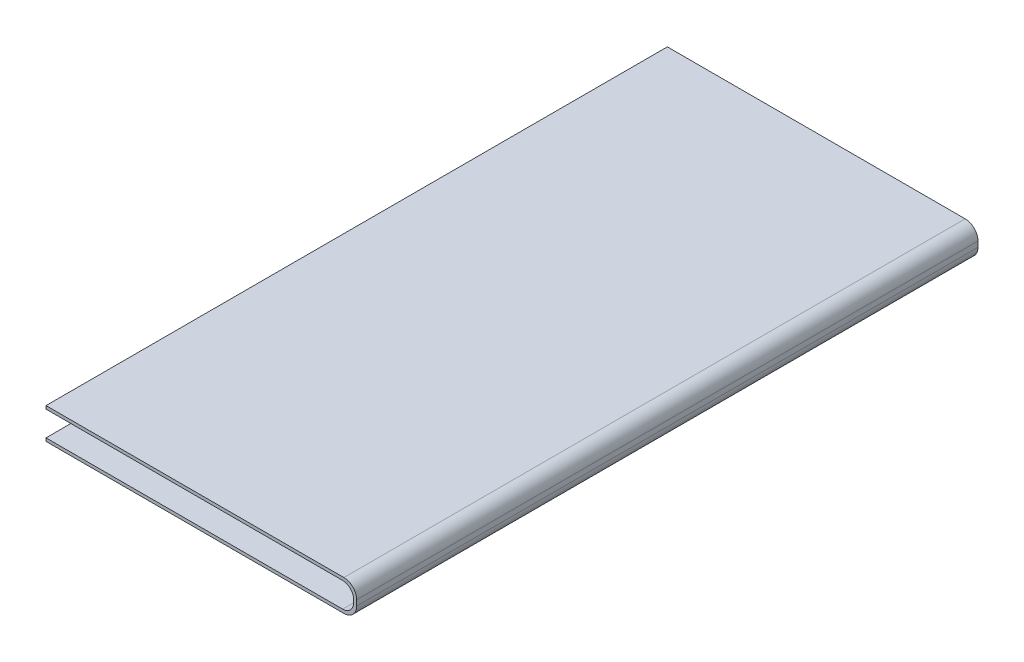
SolidWorks part; units mm, degrees
ref_plane "Спереди" through (0, 0, 0) normal (0, 0, 1) x (1, 0, 0)
ref_plane "Сверху" through (0, 0, 0) normal (0, 1, 0) x (1, 0, 0)
ref_plane "Справа" through (0, 0, 0) normal (1, 0, 0) x (0, 0, -1)
sketch "Эскиз1" plane through (0, 0, 0) normal (0, 0, 1) x (1, 0, 0)
  line L0 (14.5, -1.5) -> (24.0875, -1.5)
  line L1 (-27.5, -1.5) -> (27.5, -1.5) construction
  line L2 (24.5, -1.9125) -> (24.5, -2.0875)
  line L3 (24.0875, -2.5) -> (14.5, -2.5)
  line L4 (14.5, -1.6) -> (24.05, -1.6)
  line L5 (24.4, -1.95) -> (24.4, -2.05)
  line L6 (24.05, -2.4) -> (14.5, -2.4)
  line L7 (14.5, -1.5) -> (14.5, -1.6)
  line L8 (14.5, -2.4) -> (14.5, -2.5)
  line L9 (24, -4.1) -> (24, -1.5) construction
  line L10 (24.5, -1.5) -> (24.5, -2.5) construction
  line L11 (24.5, -2.5) -> (14.5, -2.5) construction
  line L12 (14.5, -1.5) -> (24.5, -1.5) construction
  line L13 (24.4, -1.6) -> (24.4, -2.4) construction
  line L14 (24.4, -2.4) -> (14.5, -2.4) construction
  line L15 (14.5, -1.6) -> (24.4, -1.6) construction
  arc A0 (24.5, -2.0875) -> (24.0875, -2.5) centre (24.0875, -2.0875) cw
  arc A1 (24.0875, -1.5) -> (24.5, -1.9125) centre (24.0875, -1.9125) cw
  arc A2 (24.4, -2.05) -> (24.05, -2.4) centre (24.05, -2.05) cw
  arc A3 (24.05, -1.6) -> (24.4, -1.95) centre (24.05, -1.95) cw
  point P15 (24.5, -2.5)
  dimension "D5" = 0.4125
  dimension "D6" = 0.35
  dimension "D2" = 0.5
  dimension "D3" = 1
  dimension "D4" = 10
  dimension "D1" = 0.1
extrude "Бобышка-Вытянуть1" add sketch "Эскиз1" along normal mid plane 20
